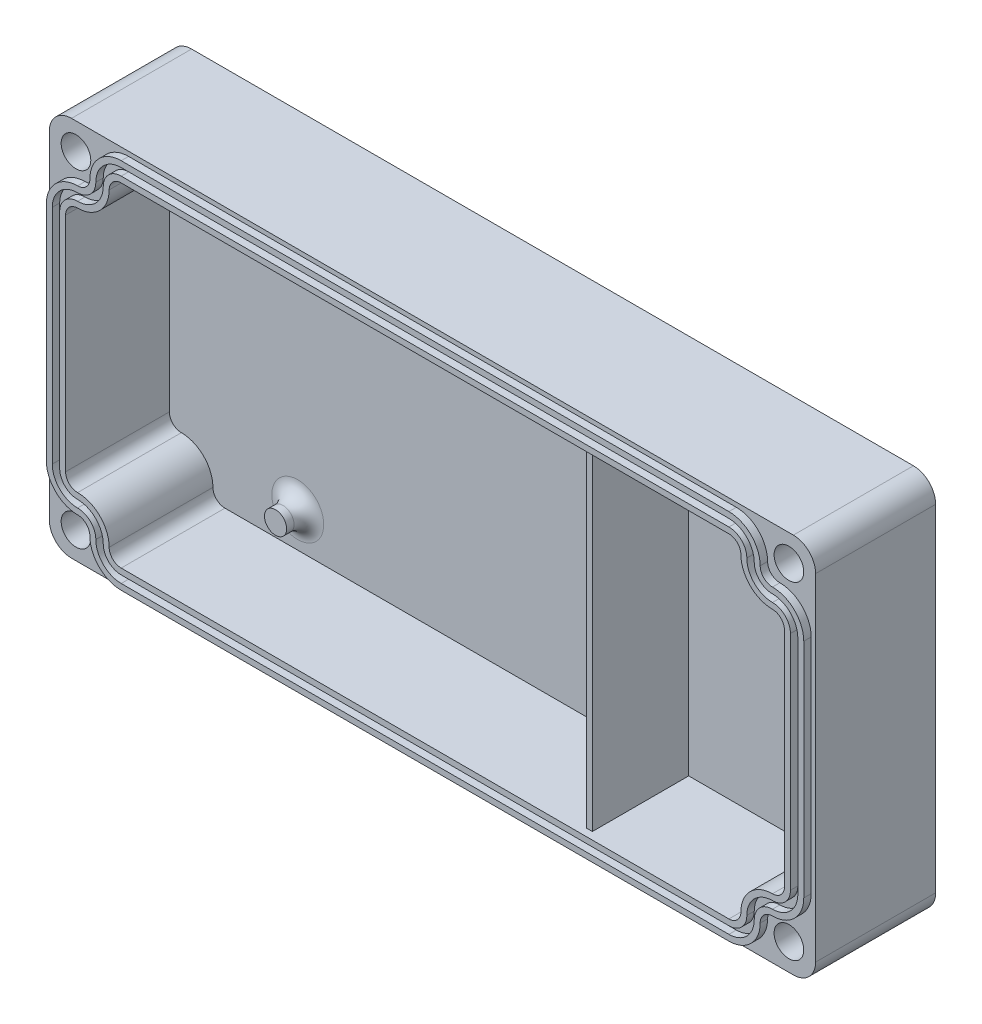
SolidWorks part; units mm, degrees
ref_plane "Plan de face" through (0, 0, 0) normal (0, 0, 1) x (1, 0, 0)
ref_plane "Plan de dessus" through (0, 0, 0) normal (0, 1, 0) x (1, 0, 0)
ref_plane "Plan de droite" through (0, 0, 0) normal (1, 0, 0) x (0, 0, -1)
sketch "Esquisse1" plane through (0, 0, 0) normal (0, 0, 1) x (1, 0, 0)
  line L1 (-48.5, 22.5) -> (48.5, 22.5)
  line L2 (-48.5, 22.5) -> (-48.5, -22.5)
  line L3 (-48.5, -22.5) -> (48.5, -22.5)
  line L4 (48.5, 22.5) -> (48.5, -22.5)
  line L5 (-48.5, 22.5) -> (48.5, -22.5) construction
  line L6 (-48.5, -22.5) -> (48.5, 22.5) construction
  point P0 (0, 0)
  dimension "D1" = 97
  dimension "D2" = 45
extrude "Boss.-Extru.1" add sketch "Esquisse1" along normal blind 13
shell "Coque1" thickness 3.2 removed face at (0, 0, 13) outward yes
ref_plane "Plan1" through (0, 0, 20) normal (0, 0, 1) x (1, 0, 0)
sketch "Esquisse8" plane through (0, 0, 20) normal (0, 0, 1) x (1, 0, 0)
  line L0 (21.5, 16.8946) -> (21.5, -12.3256)
  line L1 (48.5, -22.5) -> (48.5, 22.5) construction
  dimension "D1" = 27
sketch "Esquisse10" plane through (0, 0, 0) normal (0, 0, 1) x (1, 0, 0)
  line L0 (-48.5, 22.5) -> (-48.5, 15)
  line L1 (-48.5, 22.5) -> (-48.5, -22.5) construction
  line L2 (48.5, 22.5) -> (-48.5, 22.5) construction
  line L3 (-41, 22.5) -> (-48.5, 22.5)
  line L4 (-46.88, 15) -> (-48.5, 15) construction
  line L5 (-46.88, 15) -> (-46.88, 16.62) construction
  line L6 (-41, 20.88) -> (-42.62, 20.88) construction
  line L7 (-41, 20.88) -> (-41, 22.5) construction
  arc A1 (-48.5, 15) -> (-46.88, 16.62) centre (-46.88, 15) cw
  arc A2 (-46.88, 16.62) -> (-42.62, 20.88) centre (-46.88, 20.88) ccw
  arc A3 (-42.62, 20.88) -> (-41, 22.5) centre (-41, 20.88) cw
  dimension "D1" = 7.5
extrude "Boss.-Extru.2" add sketch "Esquisse10" along normal up to surface (13 mm away) up to face at (0, 0, 13)
mirror "Symétrie1" about plane through (0, 0, 0) normal (1, 0, 0) of "Boss.-Extru.2"
mirror "Symétrie2" about plane through (0, 0, 0) normal (0, 1, 0) of "Boss.-Extru.2"
mirror "Symétrie3" about plane through (0, 0, 0) normal (0, 1, 0) of "Symétrie1"
sketch "Esquisse13" plane through (0, 0, 13) normal (0, 0, 1) x (1, 0, 0)
  line L0 (-48.1, 22.1) -> (-48.1, 24.1) construction
  line L1 (51.7, 25.7) -> (-51.7, 25.7) construction
  line L2 (-48.1, 22.1) -> (-50.1, 22.1) construction
  line L4 (-51.7, 25.7) -> (-51.7, -25.7) construction
  circle A0 centre (-48.1, 22.1) radius 2
  circle A1 centre (-48.1, 22.1) radius 2.75 construction
  dimension "D1" = 4
  dimension "D4" = 5.5
  dimension "D2" = 1.6
  dimension "D3" = 1.6
extrude "Insert" cut sketch "Esquisse13" against normal blind 5.7
mirror "Symétrie4" about plane through (0, 0, 0) normal (1, 0, 0) of "Insert"
mirror "Symétrie5" about plane through (0, 0, 0) normal (0, 1, 0) of "Symétrie4"
sketch "Esquisse14" plane through (0, 0, 13) normal (0, 0, 1) x (1, 0, 0)
  line L0 (-41, 22.5) -> (41, 22.5)
  line L1 (48.5, 15) -> (48.5, -15)
  line L2 (41, -22.5) -> (-41, -22.5)
  line L3 (-48.5, -15) -> (-48.5, 15)
  line L4 (-50.3, -15) -> (-50.3, 15)
  line L5 (-41, 24.3) -> (41, 24.3)
  line L6 (50.3, 15) -> (50.3, -15)
  line L7 (41, -24.3) -> (-41, -24.3)
  arc A0 (41, 22.5) -> (42.62, 20.88) centre (41, 20.88) cw
  arc A1 (42.62, 20.88) -> (46.88, 16.62) centre (46.88, 20.88) ccw
  arc A2 (46.88, 16.62) -> (48.5, 15) centre (46.88, 15) cw
  arc A3 (48.5, -15) -> (46.88, -16.62) centre (46.88, -15) cw
  arc A4 (46.88, -16.62) -> (42.62, -20.88) centre (46.88, -20.88) ccw
  arc A5 (42.62, -20.88) -> (41, -22.5) centre (41, -20.88) cw
  arc A6 (-41, -22.5) -> (-42.62, -20.88) centre (-41, -20.88) cw
  arc A7 (-42.62, -20.88) -> (-46.88, -16.62) centre (-46.88, -20.88) ccw
  arc A8 (-46.88, -16.62) -> (-48.5, -15) centre (-46.88, -15) cw
  arc A9 (-48.5, 15) -> (-46.88, 16.62) centre (-46.88, 15) cw
  arc A10 (-46.88, 16.62) -> (-42.62, 20.88) centre (-46.88, 20.88) ccw
  arc A11 (-42.62, 20.88) -> (-41, 22.5) centre (-41, 20.88) cw
  arc A12 (-50.3, 15) -> (-46.88, 18.42) centre (-46.88, 15) cw
  arc A13 (-46.88, 18.42) -> (-44.42, 20.88) centre (-46.88, 20.88) ccw
  arc A14 (-44.42, 20.88) -> (-41, 24.3) centre (-41, 20.88) cw
  arc A15 (41, 24.3) -> (44.42, 20.88) centre (41, 20.88) cw
  arc A16 (44.42, 20.88) -> (46.88, 18.42) centre (46.88, 20.88) ccw
  arc A17 (46.88, 18.42) -> (50.3, 15) centre (46.88, 15) cw
  arc A18 (50.3, -15) -> (46.88, -18.42) centre (46.88, -15) cw
  arc A19 (46.88, -18.42) -> (44.42, -20.88) centre (46.88, -20.88) ccw
  arc A20 (44.42, -20.88) -> (41, -24.3) centre (41, -20.88) cw
  arc A21 (-41, -24.3) -> (-44.42, -20.88) centre (-41, -20.88) cw
  arc A22 (-44.42, -20.88) -> (-46.88, -18.42) centre (-46.88, -20.88) ccw
  arc A23 (-46.88, -18.42) -> (-50.3, -15) centre (-46.88, -15) cw
  dimension "D1" = 1.8
extrude "Extru.-Mince1" add sketch "Esquisse14" along normal blind 1 thin thin type one direction wall 0.8
fillet "Congé1" radius 3 4 edges at (-51.7, -25.7, 4.9) (51.7, -25.7, 4.9) (51.7, 25.7, 4.9) (-51.7, 25.7, 4.9)
sketch "Esquisse16" plane through (0, 0, 0) normal (0, 0, 1) x (1, 0, 0)
  circle A0 centre (-31.1716, 18.1378) radius 1.5
  circle A1 centre (14.1284, 18.1378) radius 1.5
  circle A2 centre (14.1284, -17.7622) radius 1.5
  circle A3 centre (-31.1716, -17.7622) radius 1.5
  point P0 (-31.1716, 18.1378)
  dimension "D1" = 3
  dimension "D2" = 3
  dimension "D3" = 3
  dimension "D4" = 3
extrude "Boss.-Extru.3" add sketch "Esquisse16" along normal blind 3
fillet "Congé2" radius 2 4 edges at (15.6284, -17.7622, 0) (15.6284, 18.1378, 0) (-29.6716, 18.1378, 0) (-29.6716, -17.7622, 0)
hole_wizard "Dégagement M1.61" positions "Esquisse20" profile "Esquisse19" hole size "M1.6" standard "Ansi Metric"
sketch "Esquisse20" plane through (0, 0, 3) normal (0, 0, 1) x (1, 0, 0)
  point P0 (14.1284, 18.1378)
  point P3 (14.1284, -17.7622)
  point P7 (-31.1716, 18.1378)
sketch "Esquisse19" plane through (14.1284, 18.1378, 3) normal (1, 0, 0) x (0, -1, 0)
  line L0 (0, 0) -> (0, 3.5408)
  line L1 (0, 3.5408) -> (0.9, 3)
  line L2 (0.9, 3) -> (0.9, 0)
  line L5 (0.9, 0) -> (0, 0)
  line L10 (0, 3.5408) -> (-0.9, 3) construction
  line L11 (0, -6.35) -> (0, 107.95) construction
  dimension "Diamètre du perçage" = 1.8
  dimension "Profondeur du perçage" = 3
  dimension "Angle de pointe" = 118
sketch "Esquisse17" plane through (0, 0, 13) normal (0, 0, 1) x (1, 0, 0)
  line L0 (21.5763, 9.753) -> (21.5763, -8.4958)
rib "Nervure19" sketch "Esquisse17" sketch "Esquisse17" thickness 0.8 extrusion direction normal to sketch draft on no parameters "D1"=0.8
equation "\"buse\"= 0.8"
equation "\"D1@Coque1\"=\"buse\"*4"
equation "\"hauteur\"=10"
equation "\"D1@Nervure1\"=\"hauteur\""
equation "\"D1@Nervure18\"=\"buse\""
equation "\"D2@Esquisse13\"=\"buse\"*2"
equation "\"D3@Esquisse13\"=2*\"buse\""
equation "\"D1@Esquisse14\"=\"buse\"*1+1"
